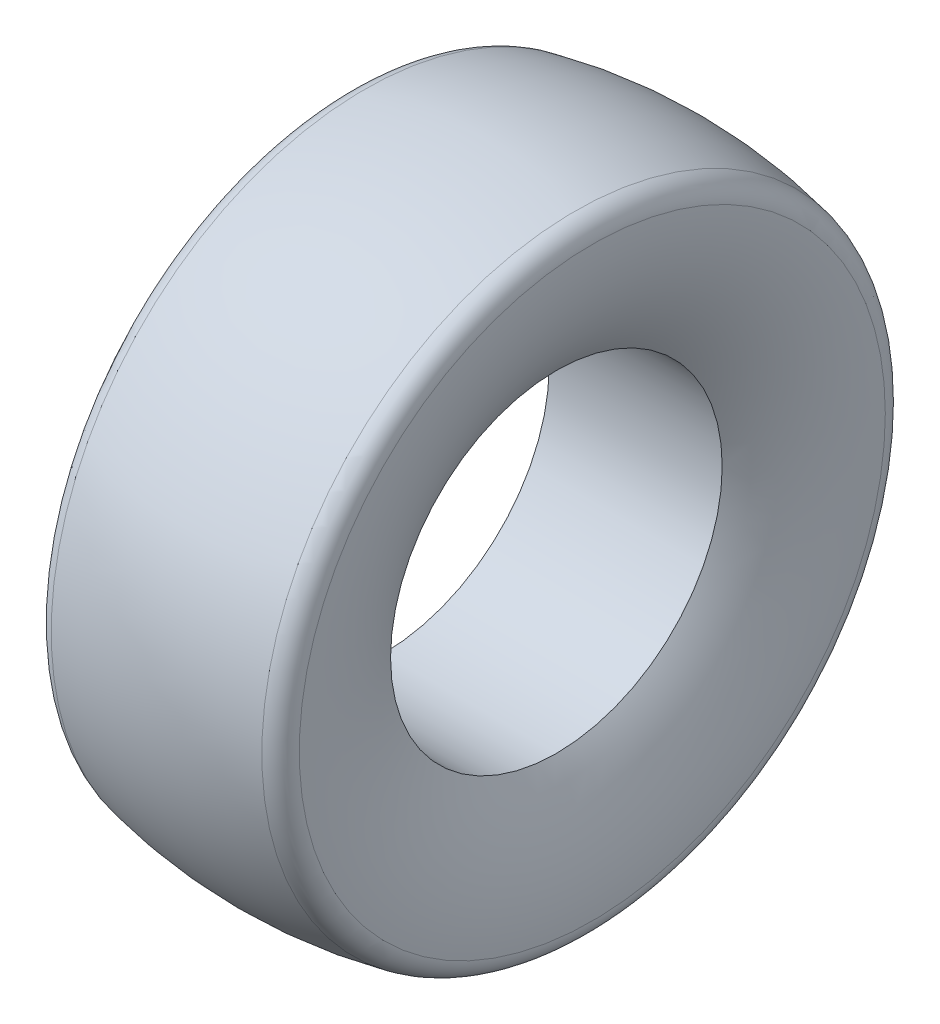
SolidWorks part; units mm, degrees
ref_plane "Front Plane" through (0, 0, 0) normal (0, 0, 1) x (1, 0, 0)
ref_plane "Top Plane" through (0, 0, 0) normal (0, 1, 0) x (1, 0, 0)
ref_plane "Right Plane" through (0, 0, 0) normal (1, 0, 0) x (0, 0, -1)
sketch "Sketch1" plane through (0, 0, 0) normal (0, 0, 1) x (1, 0, 0)
  line L0 (-12, 23) -> (12, 23)
  line L1 (0, 45) -> (0, 23) construction
  line L3 (17, 41.6727) -> (17, 23) construction
  line L4 (-17, 41.6727) -> (-17, 23) construction
  line L5 (12, 0) -> (-12, 0) construction
  arc A2 (12, 23) -> (16.9781, 40.6403) centre (-12.725, 39.5) ccw
  arc A3 (16.9781, 40.6403) -> (14.6063, 43.4592) centre (13.9803, 40.5252) ccw
  arc A4 (14.6063, 43.4592) -> (0, 45) centre (0, -25) ccw
  arc A5 (-14.6063, 43.4592) -> (0, 45) centre (0, -25) cw
  arc A6 (-16.9781, 40.6403) -> (-14.6063, 43.4592) centre (-13.9803, 40.5252) cw
  arc A7 (-12, 23) -> (-16.9781, 40.6403) centre (12.725, 39.5) cw
  point P19 (-17, 39.5)
  point P20 (17, 39.5)
  dimension "D6" = 3
  dimension "D7" = 70
  dimension "D1" = 23
  dimension "D2" = 12
  dimension "D3" = 22
  dimension "D4" = 16.5
  dimension "D5" = 34
revolve "Revolve1" add sketch "Sketch1" angle 360 about L5
sketch "Sketch2" plane through (0, 0, 0) normal (0, 1, 0) x (1, 0, 0)
  line L0 (1.3204, 2.2068) -> (-6.4891, 3.9422)
  line L1 (-6.4891, 3.9422) -> (-6.4891, 3.3641)
  line L2 (-6.4891, 3.3641) -> (-8.0227, 2.7324)
  line L3 (-6.7172, 0.8315) -> (-1.3742, 2.4075)
  line L4 (-1.3742, 2.4075) -> (-1.3742, 1.4973)
  line L5 (-1.3742, 1.4973) -> (-1.2581, 1.4462)
  line L6 (-1.2581, 1.4462) -> (1.3204, 2.2068)
  line L7 (-5.3025, -1.0686) -> (-6.1939, -2.2625)
  line L8 (-13.7642, 1.259) -> (-13.7642, 0.0362)
  arc A0 (-8.0227, 2.7324) -> (-6.7172, 0.8315) centre (-10.2872, -0.2215) cw
  arc A1 (-13.7642, 1.259) -> (-6.2348, -0.2807) centre (-12.2095, -10.3181) cw
  arc A2 (-6.2348, -0.2807) -> (-5.3025, -1.0686) centre (-8.1386, -3.479) cw
  arc A3 (-6.1939, -2.2625) -> (-13.7642, 0.0362) centre (-15.0553, -17.8305) ccw
  dimension "D1" = 8
